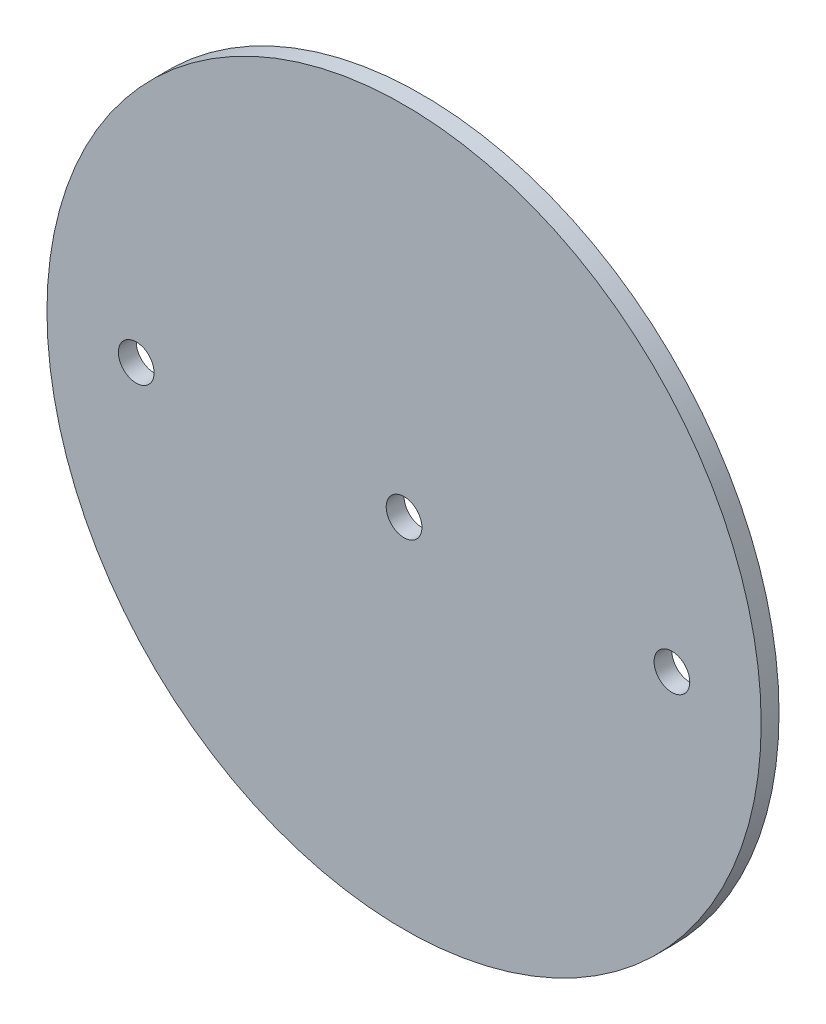
SolidWorks part; units mm, degrees
ref_plane "Front Plane" through (0, 0, 0) normal (0, 0, 1) x (1, 0, 0)
ref_plane "Top Plane" through (0, 0, 0) normal (0, 1, 0) x (1, 0, 0)
ref_plane "Right Plane" through (0, 0, 0) normal (1, 0, 0) x (0, 0, -1)
sketch "Sketch1" plane through (0, 0, 0) normal (0, 0, 1) x (1, 0, 0)
  circle A0 centre (0, 0) radius 63.5
extrude "Boss-Extrude1" add sketch "Sketch1" along normal mid plane 3.175
sketch "Sketch2" plane through (0, 0, 1.5875) normal (0, 0, 1) x (1, 0, 0)
  line L0 (-1000, 0) -> (49000, 0) construction
  point P1 (0, 0)
  point P4 (47.625, 0)
  point P5 (-47.625, 0)
  dimension "D1" = 47.625
  dimension "D2" = 95.25
hole_wizard "1/4 (0.25) Diameter Hole1" positions "Sketch2" profile "Sketch3" hole size "1/4" standard "ANSI Inch" end condition through all
sketch "Sketch3" plane through (-47.625, 0, 1.5875) normal (1, 0, 0) x (0, -1, 0)
  line L0 (0, 0) -> (0, 3.175)
  line L1 (0, 3.175) -> (3.175, 3.175)
  line L2 (3.175, 3.175) -> (3.175, 0)
  line L5 (3.175, 0) -> (0, 0)
  line L11 (0, -6.35) -> (0, 107.95) construction
  dimension "Thru Hole Dia." = 6.35
  dimension "Thru Hole Depth" = 3.175
equation "\"AIRFRAME_OD\"= 5.15in"
equation "\"AIRFRAME_ID\"= 5.00in"
equation "\"FLAT_T\"= 0.125in"
equation "\"NOSE_EXP_L\"= 27in"
equation "\"NOSE_SHOULDER_L\"= 5in"
equation "\"MAIN_L\"= 30in"
equation "\"RECO_COUP_L\"= 10in"
equation "\"RECO_SWITCH_L\"= 2in"
equation "\"DROGUE_L\"= 20in"
equation "\"ATS_FORE_COUP_L\"= 5.5in"
equation "\"ATS_AFT_COUP_L\"= 4.5in"
equation "\"LOWER_L\"= 30in"
equation "\"FIN_N\"= 4"
equation "\"CR_AFT_X\"= 0.5in"
equation "\"CR_FORE_X\"= 9.25in"
equation "\"FIN_ROOT\"= 8in"
equation "\"FIN_X\"= 0.75in"
equation "\"MOTOR_OD\"= 3.091in"
equation "\"MOTOR_ID\"= 3.00in"
equation "\"COUPLER_OD\"= 4.998in"
equation "\"COUPLER_ID\"= 4.88in"
equation "\"D1@Sketch1\"=\"AIRFRAME_ID\""
equation "\"D1@Boss-Extrude1\"=\"FLAT_T\""
equation "\"RECO_ROD_X\"= 3.5in"
equation "\"ATS_ROD_X\"= 3.75in"
equation "\"D1@Sketch2\"=\"ATS_ROD_X\"*0.5"
equation "\"D2@Sketch2\"=\"ATS_ROD_X\""
equation "\"MOTOR_L\"= 14in"
equation "\"MOTOR_LOWER_X\"= 2in"
